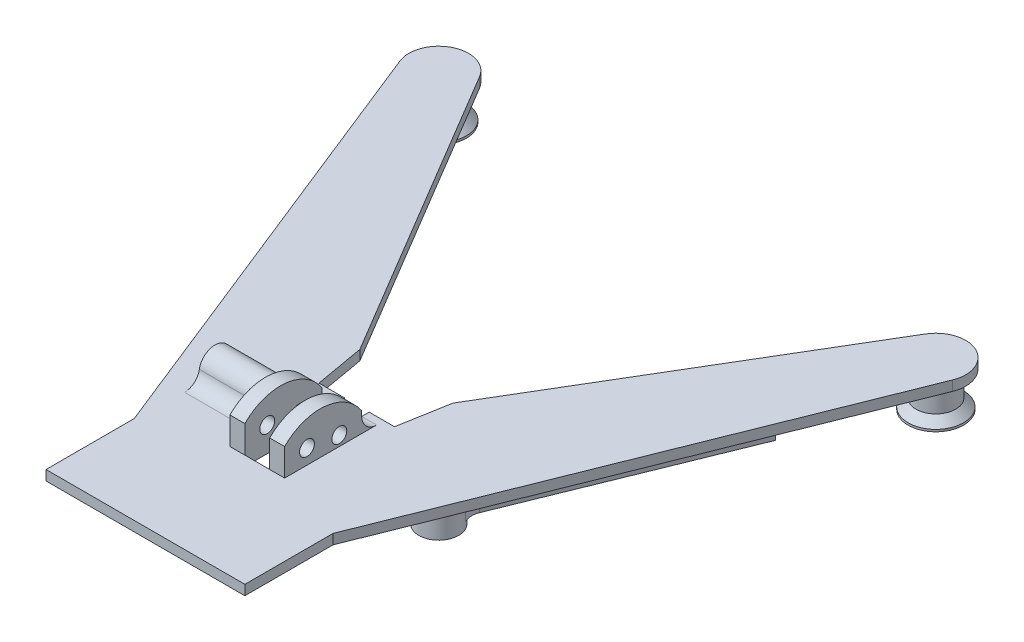
SolidWorks part; units mm, degrees
ref_plane "Front" through (0, 0, 0) normal (0, 0, 1) x (1, 0, 0)
ref_plane "Top" through (0, 0, 0) normal (0, 1, 0) x (1, 0, 0)
ref_plane "Right" through (0, 0, 0) normal (1, 0, 0) x (0, 0, -1)
ref_axis "X" through (-80.9, 0, 0) along (1, 0, 0)
ref_axis "Y" through (0, -50, 0) along (0, 1, 0)
ref_axis "Z" through (0, 0, -80.9) along (0, 0, 1)
sketch "Sketch1" plane through (0, 0, 0) normal (0, 1, 0) x (1, 0, 0)
  line L0 (-50, 0) -> (50, 0) construction
  circle A0 centre (-50, 0) radius 4
  circle A1 centre (50, 0) radius 4
  dimension "D2" = 8
  dimension "D1" = 100
extrude "Boss-Extrude1" add sketch "Sketch1" against normal blind 5
sketch "Sketch2" plane through (0, 0, 0) normal (0, 1, 0) x (1, 0, 0)
  line L0 (55.5717, -2.2262) -> (20, -91.2553)
  line L5 (44.8451, 3.0704) -> (9.3633, -56.5)
  line L6 (-44.8451, 3.0704) -> (-9.3633, -56.5)
  line L7 (-55.5717, -2.2262) -> (-20, -91.2553)
  line L8 (0, 17.0371) -> (0, 101.5315) construction
  line L9 (20, -91.2553) -> (20, -109)
  line L10 (20, -109) -> (-20, -109)
  line L11 (-20, -109) -> (-20, -91.2553)
  line L12 (2.5, -86.5) -> (-2.5, -86.5)
  line L14 (2.5, -86.5) -> (2.5, -66.5)
  line L15 (-2.5, -66.5) -> (-2.5, -86.5)
  line L16 (9.3633, -56.5) -> (7.6, -66.5)
  line L17 (-9.3633, -56.5) -> (-7.6, -66.5)
  line L18 (7.6, -66.5) -> (2.5, -66.5)
  line L19 (-7.6, -66.5) -> (-2.5, -66.5)
  arc A0 (55.5717, -2.2262) -> (44.8451, 3.0704) centre (50, 0) ccw
  arc A1 (-44.8451, 3.0704) -> (-55.5717, -2.2262) centre (-50, 0) ccw
  point P24 (8.7155, -58.1046)
  dimension "D1" = 6
  dimension "D2" = 86.5
  dimension "D3" = 5
  dimension "D4" = 10
  dimension "D5" = 109
  dimension "D6" = 40
  dimension "D7" = 15.2
  dimension "D8" = 20
  dimension "D9" = 100
  dimension "D10" = 9
extrude "Boss-Extrude2" add sketch "Sketch2" along normal blind 2
sketch "Sketch3" plane through (0, -5, 0) normal (0, -1, 0) x (1, 0, 0)
  circle A0 centre (50, 0) radius 4
  circle A1 centre (-50, 0) radius 4
  circle A2 centre (50, 0) radius 4 construction
  circle A3 centre (-50, 0) radius 4 construction
extrude "Boss-Extrude3" add sketch "Sketch3" along normal blind 2 draft 45 draft outward yes
chamfer "Chamfer1" distance 0.6 angle 45 2 edges at (-50, -7, -6) (50, -7, -6) first distance on face at (-50, -7, -6) first distance on face at (50, -7, -6)
fillet "Fillet1" radius 1 2 edges at (50, 0, 4) (-50, 0, 4)
sketch "Sketch5" plane through (0, 0, 0) normal (1, 0, 0) x (0, 0, -1)
  line L1 (-86.5, 7.5) -> (-86.5, 2)
  line L2 (-91.2553, 2) -> (-109, 2) construction
  line L3 (-71, 6) -> (-71, 2)
  line L4 (-71, 2) -> (-86.5, 2)
  line L5 (-2.2262, 2) -> (-91.2553, 2) construction
  line L6 (-82, 5) -> (-75.5, 5) construction
  line L7 (-75.5, 5) -> (-75.5, 4) construction
  circle A0 centre (-82, 5) radius 1.5
  arc A1 (-71, 6) -> (-86.5, 7.5) centre (-79.3555, 0.4928) ccw
  circle A2 centre (-75.5, 4) radius 1.5
  dimension "D1" = 3
  dimension "D2" = 3
  dimension "D3" = 82
  dimension "D5" = 11
  dimension "D6" = 8.5
  dimension "D4" = 4.5
  dimension "D7" = 5.5
  dimension "D8" = 4
  dimension "D9" = 6.5
  dimension "D10" = 1
extrude "Boss-Extrude4" add sketch "Sketch5" against normal blind 3 from offset 2.5 offset against normal yes
fillet "Fillet2" radius 3 1 edges at (-4, 2, 71)
mirror "Mirror1" about plane through (0, 0, 0) normal (1, 0, 0) of "Fillet2", "Boss-Extrude4"
sketch "Sketch6" plane through (-5.5, 0, 0) normal (-1, 0, 0) x (0, 0, 1)
  line L0 (72.3, 2) -> (72.3, 4)
  line L1 (86.5, 2) -> (68, 2) construction
  line L2 (78.7, 4) -> (78.7, 2)
  line L3 (78.7, 2) -> (72.3, 2)
  arc A0 (72.3, 4) -> (78.7, 4) centre (75.5, 4) cw
  circle A1 centre (75.5, 4) radius 1.5 construction
  circle A2 centre (75.5, 4) radius 1.5
  dimension "D1" = 6.4
extrude "Boss-Extrude5" add sketch "Sketch6" along normal blind 14
fillet "Fillet3" radius 3 2 edges at (-12.5, 2, 78.7) (-12.5, 2, 72.3)
sketch "Sketch7" plane through (0, 0, 0) normal (0, -1, 0) x (1, 0, 0)
  line L0 (0, 0) -> (0, 70) construction
  line L1 (-20, 70) -> (20, 70) construction
  circle A0 centre (-20, 70) radius 4
  circle A1 centre (20, 70) radius 4
  point P7 (0, 0)
  dimension "D3" = 8
  dimension "D1" = 40
  dimension "D2" = 70
extrude "Boss-Extrude6" add sketch "Sketch7" along normal blind 7
sketch "Sketch8" plane through (0, 0, 0) normal (0, -1, 0) x (1, 0, 0)
  line L0 (0, 0) -> (0, 184.7097) construction
  line L1 (-20, 70) -> (-42.9164, 25.5608) construction
  line L2 (20, 70) -> (42.9164, 25.5608) construction
  line L3 (-20.8888, 70.4583) -> (-43.8052, 26.0192)
  line L4 (19.1112, 69.5417) -> (42.0276, 25.1025)
  line L5 (-19.1112, 69.5417) -> (-42.0276, 25.1025)
  line L6 (20.8888, 70.4583) -> (43.8052, 26.0192)
  line L7 (-20.8888, 70.4583) -> (-19.1112, 69.5417)
  line L8 (-43.8052, 26.0192) -> (-42.0276, 25.1025)
  line L9 (19.1112, 69.5417) -> (20.8888, 70.4583)
  line L10 (42.0276, 25.1025) -> (43.8052, 26.0192)
  line L13 (-20, 70) -> (-42.9164, 25.5608) construction
  line L14 (20, 70) -> (42.9164, 25.5608) construction
  line L17 (20, 91.2553) -> (55.5717, 2.2262) construction
  line L18 (-55.5717, 2.2262) -> (-20, 91.2553) construction
  point P2 (40.5357, 21.4461)
  point P19 (-39.6159, 24.0085)
  point P23 (39.6149, 24.0085)
  point P24 (-39.6212, 24.0108)
  point P25 (-39.6159, 21.1908)
  point P26 (39.0258, 25.3921)
  point P27 (40.5357, 24.4008)
  point P28 (39.6159, 24.0085)
  point P29 (-39.6159, 24.0085)
  point P30 (-38.8166, 23.6162)
  point P31 (39.7701, 24.0521)
  point P36 (42.4667, 25.3318)
  dimension "D3" = 50
  dimension "D4" = 5.5
  dimension "D5" = 5.5
  dimension "D1" = 1
  dimension "D2" = 1
extrude "Boss-Extrude7" add sketch "Sketch8" along normal blind 6
fillet "Fillet4" radius 3 4 edges at (22.6639, -3, 67.0161) (20.8863, -3, 66.0994) (-22.6639, -3, 67.0161) (-20.8863, -3, 66.0994)
chamfer "Chamfer2" distance 50 angle 4 2 edges at (-42.9164, -6, 25.5608) (42.9164, -6, 25.5608) first distance on face at (-29.0486, -6, 52.453) first distance on face at (29.0486, -6, 52.453)
